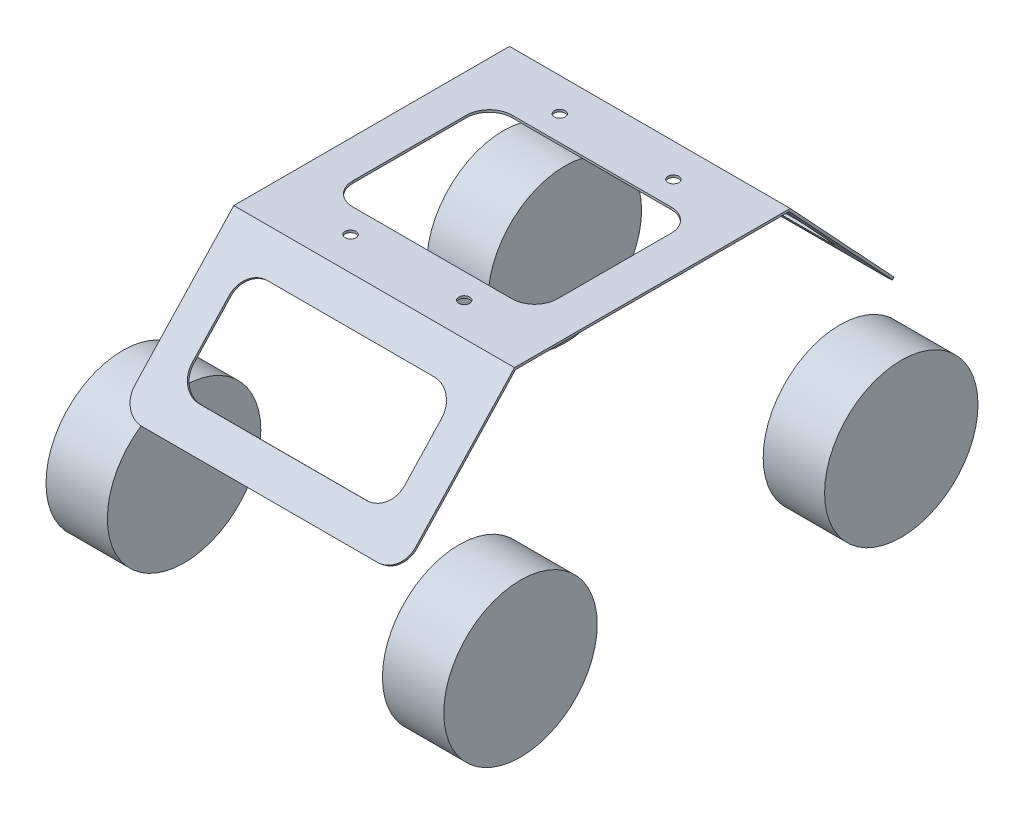
SolidWorks part; units mm, degrees
ref_plane "Plano frontal" through (0, 0, 0) normal (0, 0, 1) x (1, 0, 0)
ref_plane "Plano superior" through (0, 0, 0) normal (0, 1, 0) x (1, 0, 0)
ref_plane "Plano direito" through (0, 0, 0) normal (1, 0, 0) x (0, 0, -1)
sketch "Esboço1" plane through (0, 0, 0) normal (0, 1, 0) x (1, 0, 0)
  line L1 (-87.5, 117.5) -> (87.5, 117.5)
  line L2 (-87.5, 117.5) -> (-87.5, -117.5)
  line L3 (-87.5, -117.5) -> (87.5, -117.5)
  line L4 (87.5, 117.5) -> (87.5, -117.5)
  line L5 (-87.5, 117.5) -> (87.5, -117.5) construction
  line L6 (-87.5, -117.5) -> (87.5, 117.5) construction
  point P0 (0, 0)
  dimension "D1" = 175
  dimension "D2" = 235
extrude "Ressalto-extrusão1" add sketch "Esboço1" along normal blind 67.5
fillet "Filete1" radius 33.75 4 edges at (0, 0, -117.5) (0, 67.5, -117.5) (0, 0, 117.5) (0, 67.5, 117.5)
sketch "Esboço2" plane through (87.5, 0, 0) normal (1, 0, 0) x (0, 0, -1)
  line L0 (-83.75, 67.5) -> (83.75, 67.5)
  line L1 (83.75, 67.5) -> (83.75, 0) construction
  line L2 (83.75, 0) -> (-83.75, 0)
  line L3 (-83.75, 0) -> (-83.75, 67.5) construction
  circle A0 centre (-83.75, 33.75) radius 33.75 construction
  circle A1 centre (83.75, 33.75) radius 33.75 construction
  arc A2 (-83.75, 67.5) -> (-83.75, 0) centre (-83.75, 33.75) cw
  arc A3 (83.75, 67.5) -> (83.75, 0) centre (83.75, 33.75) ccw
extrude "Corte-extrusão1" cut sketch "Esboço2" against normal through all
sketch "Esboço3" plane through (0, 0, 0) normal (0, 0, 1) x (1, 0, 0)
  line L0 (87.5, 33.75) -> (-87.5, 33.75) construction
  line L1 (-60.5, 67.5) -> (60.5, 67.5)
  line L2 (-60.5, 67.5) -> (-60.5, 0)
  line L3 (-60.5, 0) -> (60.5, 0)
  line L4 (60.5, 67.5) -> (60.5, 0)
  line L5 (-60.5, 67.5) -> (60.5, 0) construction
  line L6 (-60.5, 0) -> (60.5, 67.5) construction
  line L7 (-87.5, 0) -> (87.5, 0) construction
  line L8 (87.5, 0) -> (87.5, 67.5) construction
  point P0 (0, 33.75)
  dimension "D1" = 27
extrude "Corte-extrusão2" cut sketch "Esboço3" against normal through all and the other way through all
ref_plane "Plano1" through (0, 70, 0) normal (0, 1, 0) x (1, 0, 0)
sketch "Esboço4" plane through (0, 70, 0) normal (0, 1, 0) x (1, 0, 0)
  line L1 (-61.75, 111) -> (61.75, 111)
  line L2 (-61.75, 111) -> (-61.75, -111)
  line L3 (-61.75, -111) -> (61.75, -111)
  line L4 (61.75, 111) -> (61.75, -111)
  line L5 (-61.75, 111) -> (61.75, -111) construction
  line L6 (-61.75, -111) -> (61.75, 111) construction
  point P0 (0, 0)
  dimension "D1" = 123.5
  dimension "D2" = 222
extrude "Ressalto-extrusão2" add sketch "Esboço4" along normal blind 54 separate body
sketch "Esboço6" plane through (61.75, 0, 0) normal (1, 0, 0) x (0, 0, -1)
  line L0 (-111, 70) -> (-111, 124)
  line L1 (-111, 124) -> (-60.6442, 124)
  line L2 (-111, 124) -> (111, 124) construction
  line L3 (-60.6442, 124) -> (-111, 70)
  line L4 (111, 124) -> (111, 70)
  line L5 (111, 70) -> (60.6442, 124)
  line L6 (60.6442, 124) -> (111, 124)
  line L7 (-109.6327, 70) -> (-60.2094, 123)
  line L8 (-111, 70) -> (111, 70) construction
  line L9 (-60.2094, 123) -> (60.2094, 123)
  line L10 (60.2094, 123) -> (109.6327, 70)
  line L11 (109.6327, 70) -> (-109.6327, 70)
  dimension "D1" = 43
  dimension "D2" = 1
  dimension "D3" = 1
  dimension "D4" = 1
extrude "Corte-extrusão3" cut sketch "Esboço6" against normal through all
sketch "Esboço7" plane through (0, 124, 0) normal (0, 1, 0) x (1, 0, 0)
  line L0 (-25, 46) -> (-25, -46) construction
  line L1 (-35, 35) -> (35, 35)
  line L2 (-45, 25) -> (-45, -25)
  line L3 (-35, -35) -> (35, -35)
  line L4 (45, 25) -> (45, -25)
  line L5 (-45, 35) -> (45, -35) construction
  line L6 (-45, -35) -> (45, 35) construction
  line L7 (-25, 46) -> (25, 46) construction
  line L8 (-25, -46) -> (25, -46) construction
  line L9 (25, 46) -> (25, -46) construction
  line L10 (-25, -46) -> (25, 46) construction
  line L11 (-25, 46) -> (25, -46) construction
  arc A0 (35, -35) -> (45, -25) centre (35, -25) ccw
  arc A1 (-45, -25) -> (-35, -35) centre (-35, -25) ccw
  arc A2 (35, 35) -> (45, 25) centre (35, 25) cw
  arc A3 (-35, 35) -> (-45, 25) centre (-35, 25) ccw
  circle A4 centre (-25, -46) radius 2.4
  circle A5 centre (25, -46) radius 2.4
  circle A6 centre (-25, 46) radius 2.4
  circle A7 centre (25, 46) radius 2.4
  point P0 (0, 0)
  dimension "D3" = 10
  dimension "D6" = 4.8
  dimension "D1" = 70
  dimension "D2" = 90
  dimension "D4" = 92
  dimension "D5" = 50
extrude "Corte-extrusão4" cut sketch "Esboço7" against normal through all
sketch "Esboço8" plane through (0, 87.9233, -94.2862) normal (0, 0.682, -0.7314) x (-1, 0, 0)
  line L0 (61.75, 49.3286) -> (61.75, -24.5071) construction
  line L1 (-36.75, 34.3286) -> (36.75, 34.3286)
  line L2 (-46.75, 24.3286) -> (-46.75, 0.4929)
  line L3 (-36.75, -9.5071) -> (36.75, -9.5071)
  line L4 (46.75, 24.3286) -> (46.75, 0.4929)
  line L5 (-46.75, 34.3286) -> (46.75, -9.5071) construction
  line L6 (-46.75, -9.5071) -> (46.75, 34.3286) construction
  line L7 (-61.75, 49.3286) -> (-61.75, -24.5071) construction
  line L8 (61.75, 49.3286) -> (-61.75, 49.3286) construction
  line L9 (-61.75, -24.5071) -> (61.75, -24.5071) construction
  line L13 (0, 12.4108) -> (0, -24.5071) construction
  arc A0 (36.75, -9.5071) -> (46.75, 0.4929) centre (36.75, 0.4929) ccw
  arc A1 (-46.75, 0.4929) -> (-36.75, -9.5071) centre (-36.75, 0.4929) ccw
  arc A2 (36.75, 34.3286) -> (46.75, 24.3286) centre (36.75, 24.3286) cw
  arc A3 (-36.75, 34.3286) -> (-46.75, 24.3286) centre (-36.75, 24.3286) ccw
  arc A4 (51.75, -24.5071) -> (61.75, -14.5071) centre (51.75, -14.5071) ccw
  arc A5 (-61.75, -14.5071) -> (-51.75, -24.5071) centre (-51.75, -14.5071) ccw
  point P0 (0, 12.4108)
  point P36 (61.75, -24.5071)
  point P39 (-61.75, -24.5071)
  line M2 (-61.75, 49.3286) -> (-61.75, -24.5071)
  line M3 (-61.75, -24.5071) -> (61.75, -24.5071)
  line M4 (61.75, -24.5071) -> (61.75, 49.3286)
  dimension "D5" = 10
  dimension "D6" = 10
  dimension "D1" = 15
  dimension "D2" = 15
  dimension "D3" = 15
  dimension "D4" = 15
extrude "Corte-extrusão5" cut sketch "Esboço8" against normal blind 10 contours L1 A3 L2 A1 L3 A0 L4 A2 | A5 M2 M3 | A4 M3 M4 region at (0, 97, -85.8221) region at (59.5163, 71.6336, -109.4766) region at (-59.5163, 71.6336, -109.4766)
mirror "Espelhar1" about plane through (0, 0, 0) normal (0, 0, 1) of "Corte-extrusão5"
